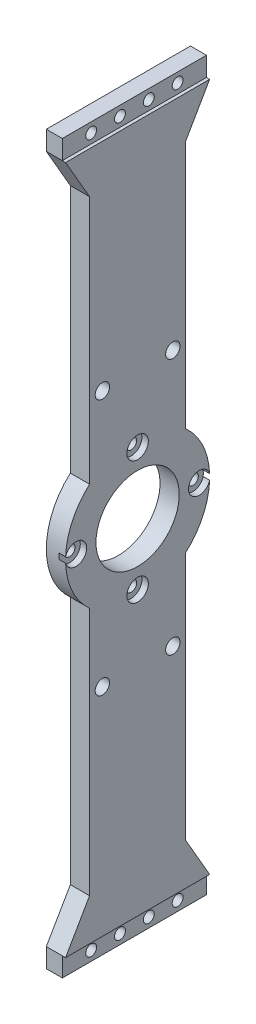
SolidWorks part; units mm, degrees
material "Сплав 2024"
ref_plane "Спереди" through (0, 0, 0) normal (0, 0, 1) x (1, 0, 0)
ref_plane "Сверху" through (0, 0, 0) normal (0, 1, 0) x (1, 0, 0)
ref_plane "Справа" through (0, 0, 0) normal (1, 0, 0) x (0, 0, -1)
sketch "Эскиз1" plane through (0, 0, 0) normal (0, 1, 0) x (1, 0, 0)
  line L1 (0, 0) -> (6, 0)
  line L2 (0, 0) -> (0, -30)
  line L3 (0, -30) -> (6, -30)
  line L4 (6, 0) -> (6, -30)
  dimension "D1" = 6
  dimension "D2" = 30
extrude "Бобышка-Вытянуть1" add sketch "Эскиз1" along normal blind 227
sketch "Эскиз2" plane through (0, 0, 0) normal (-1, 0, 0) x (0, 0, 1)
  line L0 (30, 113.5) -> (0, 113.5) construction
  line L1 (30, 227) -> (30, 0) construction
  line L2 (0, 227) -> (0, 0) construction
  line L3 (15, 227) -> (15, 0) construction
  line L4 (0, 227) -> (30, 227) construction
  line L5 (0, 0) -> (30, 0) construction
  circle A0 centre (15, 113.5) radius 22.5
  dimension "D1" = 45
extrude "Бобышка-Вытянуть2" add sketch "Эскиз2" against normal up to surface (6 mm away) up to face at (6, 113.5, 15)
sketch "Эскиз3" plane through (0, 0, 0) normal (-1, 0, 0) x (0, 0, 1)
  circle A0 centre (15, 113.5) radius 13
  dimension "D1" = 26
extrude "Вырез-Вытянуть1" cut sketch "Эскиз3" against normal through all
sketch "Эскиз4" plane through (6, 0, 0) normal (-1, 0, 0) x (0, 0, 1)
  line L0 (15, 136) -> (15, 91) construction
  line L1 (15, 227) -> (15, 0) construction
  line L2 (37.5, 113.5) -> (-7.5, 113.5) construction
  circle A0 centre (15, 113.5) radius 19.25 construction
  circle A1 centre (15, 113.5) radius 22.5 construction
  dimension "D1" = 38.5
hole_wizard "Цековка для  винта с полукруглой головкой M31" positions "Эскиз6" profile "Эскиз5" counterbore size "M3" standard "Ansi Metric" end condition through all
sketch "Эскиз6" plane through (6, -25.0247, 7.2629) normal (-1, 0, 0) x (0, 0, 1)
  line L0 (7.7371, 161.0247) -> (7.7371, 116.0247) construction
  line L1 (30.2371, 138.5247) -> (-14.7629, 138.5247) construction
  circle A0 centre (7.7371, 138.5247) radius 19.25 construction
  point P0 (7.7371, 157.7747)
  point P6 (-11.5129, 138.5247)
  point P10 (7.7371, 119.2747)
  point P12 (26.9871, 138.5247)
sketch "Эскиз5" plane through (6, 132.75, 15) normal (0, 1, 0) x (0, 0, -1)
  line L0 (0, 0) -> (0, 6)
  line L1 (0, 6) -> (1.7, 6)
  line L3 (1.7, 6) -> (1.7, 2)
  line L4 (1.7, 2) -> (3.35, 2)
  line L5 (3.35, 2) -> (3.35, 0)
  line L7 (3.35, 0) -> (0, 0)
  line L11 (0, -6.35) -> (0, 107.95) construction
  dimension "Диаметр сквозного отверстия" = 3.4
  dimension "Глубина сквозного отверстия" = 6
  dimension "Диаметр цековки" = 6.7
  dimension "Глубина цековки" = 2
sketch "Эскиз8" plane through (6, 0, 0) normal (1, 0, 0) x (0, 0, -1)
  line L0 (-15, 227) -> (-15, 0) construction
  line L1 (-30, 227) -> (0, 227) construction
  line L2 (-30, 0) -> (0, 0) construction
  line L3 (19.447, 113.5) -> (-49.447, 113.5) construction
  line L4 (0, 227) -> (0, 130.2705) construction
  line L5 (-26, 153.5) -> (-4, 153.5) construction
  line L6 (-26, 153.5) -> (-26, 73.5) construction
  line L7 (-26, 73.5) -> (-4, 73.5) construction
  line L8 (-4, 153.5) -> (-4, 73.5) construction
  line L9 (-26, 153.5) -> (-4, 73.5) construction
  line L10 (-26, 73.5) -> (-4, 153.5) construction
  point P8 (-15, 113.5)
  point P9 (-15, 113.5)
  dimension "D1" = 4
  dimension "D2" = 80
hole_wizard "Отверстие с зазором M41" positions "Эскиз10" profile "Эскиз9" hole size "M4" standard "Ansi Metric" end condition through all
sketch "Эскиз10" plane through (6, 0, 0) normal (1, 0, 0) x (0, 0, -1)
  point P0 (-26, 153.5)
  point P3 (-4, 153.5)
  point P6 (-4, 73.5)
  point P9 (-26, 73.5)
sketch "Эскиз9" plane through (6, 153.5, 26) normal (0, 1, 0) x (0, 0, -1)
  line L0 (0, 0) -> (0, 6)
  line L1 (0, 6) -> (2.25, 6)
  line L2 (2.25, 6) -> (2.25, 0)
  line L5 (2.25, 0) -> (0, 0)
  line L11 (0, -6.35) -> (0, 107.95) construction
  dimension "Диаметр сквозного отверстия" = 4.5
  dimension "Глубина сквозного отверстия" = 6
sketch "Эскиз11" plane through (6, 0, 0) normal (1, 0, 0) x (0, 0, -1)
  line L0 (-15, 227) -> (-15, 0) construction
  line L1 (-30, 227) -> (0, 227) construction
  line L2 (-30, 0) -> (0, 0) construction
  line L3 (-37.5, 221) -> (-30, 208.0096)
  line L4 (-37.5, 221) -> (7.5, 221) construction
  line L5 (-37.5, 221) -> (-37.5, 227)
  line L6 (-37.5, 227) -> (7.5, 227)
  line L7 (7.5, 221) -> (7.5, 227)
  line L8 (-37.5, 221) -> (7.5, 227) construction
  line L9 (-37.5, 227) -> (7.5, 221) construction
  line L10 (-30, 227) -> (-30, 130.2705) construction
  line L11 (-30, 208.0096) -> (0, 208.0096)
  line L12 (0, 227) -> (0, 130.2705) construction
  line L13 (0, 208.0096) -> (7.5, 221)
  line L14 (-37.5, 224) -> (7.5, 224) construction
  line L15 (-28.5, 227) -> (-28.5, 221) construction
  line L16 (-19.5, 227) -> (-19.5, 221) construction
  line L17 (-10.5, 227) -> (-10.5, 221) construction
  line L18 (-1.5, 227) -> (-1.5, 221) construction
  line L19 (-15, 113.5) -> (-5.455, 113.5) construction
  line L20 (-1.5, 0) -> (-1.5, 6) construction
  line L21 (-10.5, 0) -> (-10.5, 6) construction
  line L22 (-19.5, 0) -> (-19.5, 6) construction
  line L23 (-28.5, 0) -> (-28.5, 6) construction
  line L24 (-37.5, 3) -> (7.5, 3) construction
  line L25 (-37.5, 0) -> (7.5, 6) construction
  line L26 (-37.5, 6) -> (7.5, 0) construction
  line L27 (-37.5, 6) -> (7.5, 6) construction
  line L28 (0, 18.9904) -> (7.5, 6)
  line L29 (-30, 18.9904) -> (0, 18.9904)
  line L30 (7.5, 6) -> (7.5, 0)
  line L31 (-37.5, 0) -> (7.5, 0)
  line L32 (-37.5, 6) -> (-37.5, 0)
  line L33 (-37.5, 6) -> (-30, 18.9904)
  point P6 (-15, 224)
  point P45 (-15, 3)
  dimension "D1" = 6
  dimension "D2" = 45
  dimension "D3" = 120
  dimension "D4" = 9
  dimension "D5" = 9
  dimension "D6" = 9
  dimension "D7" = 9
extrude "Бобышка-Вытянуть3" add sketch "Эскиз11" against normal up to surface (6 mm away) up to face at (0, 153.5, 23.75)
hole_wizard "Отверстие с зазором M31" positions "Эскиз13" profile "Эскиз12" hole size "M3" standard "Ansi Metric" end condition through all
sketch "Эскиз13" plane through (6, 0, 0) normal (1, 0, 0) x (0, 0, -1)
  line L0 (-28.5, 227) -> (-28.5, 221) construction
  line L1 (-19.5, 227) -> (-19.5, 221) construction
  line L2 (-10.5, 227) -> (-10.5, 221) construction
  line L3 (-1.5, 227) -> (-1.5, 221) construction
  line L4 (-28.5, 0) -> (-28.5, 6) construction
  line L5 (-19.5, 0) -> (-19.5, 6) construction
  line L6 (-10.5, 0) -> (-10.5, 6) construction
  line L7 (-1.5, 0) -> (-1.5, 6) construction
  point P0 (-28.5, 224)
  point P4 (-19.5, 224)
  point P8 (-10.5, 224)
  point P12 (-1.5, 224)
  point P16 (-28.5, 3)
  point P20 (-19.5, 3)
  point P24 (-10.5, 3)
  point P28 (-1.5, 3)
sketch "Эскиз12" plane through (6, 224, 28.5) normal (0, 1, 0) x (0, 0, -1)
  line L0 (0, 0) -> (0, 6)
  line L1 (0, 6) -> (1.7, 6)
  line L2 (1.7, 6) -> (1.7, 0)
  line L5 (1.7, 0) -> (0, 0)
  line L11 (0, -6.35) -> (0, 107.95) construction
  dimension "Диаметр сквозного отверстия" = 3.4
  dimension "Глубина сквозного отверстия" = 6
sketch "Эскиз14" plane through (6, 0, 0) normal (1, 0, 0) x (0, 0, -1)
  line L1 (-37.5, 227) -> (7.5, 227)
  line L2 (-37.5, 227) -> (-37.5, 221)
  line L3 (-37.5, 221) -> (7.5, 221)
  line L4 (7.5, 227) -> (7.5, 221)
  line L5 (-37.5, 0) -> (7.5, 0)
  line L6 (-37.5, 0) -> (-37.5, 6)
  line L7 (-37.5, 6) -> (7.5, 6)
  line L8 (7.5, 0) -> (7.5, 6)
extrude "Вырез-Вытянуть2" cut sketch "Эскиз14" against normal blind 1
equation "\"D4@Эскиз11\"=\"D2@Эскиз11\"/5"
equation "\"D5@Эскиз11\"=\"D4@Эскиз11\""
equation "\"D6@Эскиз11\"=\"D4@Эскиз11\""
equation "\"D7@Эскиз11\"=\"D4@Эскиз11\""
